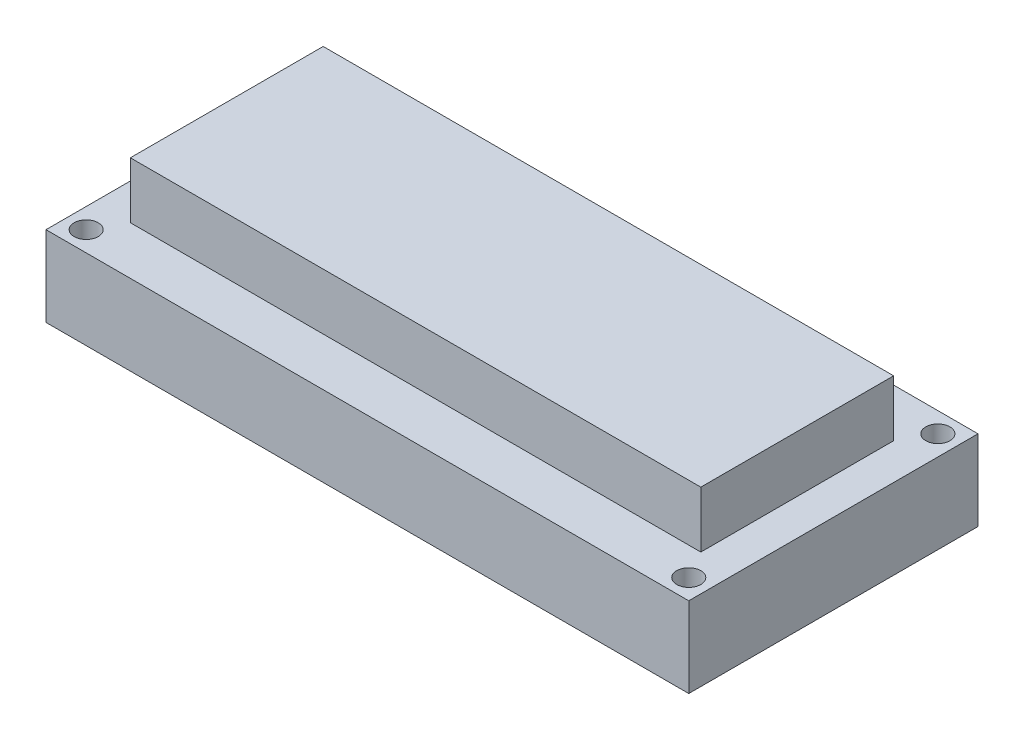
SolidWorks part; units mm, degrees
ref_plane "Front Plane" through (0, 0, 0) normal (0, 0, 1) x (1, 0, 0)
ref_plane "Top Plane" through (0, 0, 0) normal (0, 1, 0) x (1, 0, 0)
ref_plane "Right Plane" through (0, 0, 0) normal (1, 0, 0) x (0, 0, -1)
sketch "Sketch1" plane through (0, 0, 0) normal (0, 1, 0) x (1, 0, 0)
  line L1 (40, -18) -> (-40, -18)
  line L2 (40, -18) -> (40, 18)
  line L3 (40, 18) -> (-40, 18)
  line L4 (-40, -18) -> (-40, 18)
  line L5 (40, -18) -> (-40, 18) construction
  line L6 (40, 18) -> (-40, -18) construction
  line L7 (35.5, -12) -> (-35.5, -12)
  line L8 (35.5, -12) -> (35.5, 12)
  line L9 (35.5, 12) -> (-35.5, 12)
  line L10 (-35.5, -12) -> (-35.5, 12)
  line L11 (35.5, -12) -> (-35.5, 12) construction
  line L12 (35.5, 12) -> (-35.5, -12) construction
  line L13 (-37.5, -15.5) -> (37.5, -15.5) construction
  line L14 (-37.5, -15.5) -> (-37.5, 15.5) construction
  line L15 (-37.5, 15.5) -> (37.5, 15.5) construction
  line L16 (37.5, -15.5) -> (37.5, 15.5) construction
  line L17 (-37.5, -15.5) -> (37.5, 15.5) construction
  line L18 (-37.5, 15.5) -> (37.5, -15.5) construction
  circle A0 centre (37.5, 15.5) radius 1.5
  circle A1 centre (37.5, -15.5) radius 1.5
  circle A2 centre (-37.5, -15.5) radius 1.5
  circle A3 centre (-37.5, 15.5) radius 1.5
  point P0 (0, 0)
  point P6 (0, 0)
  point P11 (0, 0)
  dimension "D7" = 3
  dimension "D1" = 36
  dimension "D2" = 80
  dimension "D3" = 71
  dimension "D4" = 24
  dimension "D5" = 31
  dimension "D6" = 75
extrude "Boss-Extrude1" add sketch "Sketch1" against normal blind 10 contours L10 L7 L8 L9 | L4 L1 L2 L3 A3 A2 A1 A0 L7 L10 L9 L8 region at (0, 0, 17.1227) region at (0, 0, 0)
extrude "Boss-Extrude2" add sketch "Sketch1<3>" along normal blind 7 contours L10 L7 L8 L9 region at (0, 0, 0)
sketch "Sketch1<3>" plane through (0, 0, 0) normal (0, 1, 0) x (1, 0, 0) same geometry as "Sketch1"
sketch "Sketch2" plane through (0, 0, 0) normal (0, 1, 0) x (1, 0, 0)
  line L0 (-35.5, -12) -> (-35.5, 12) construction
  line L1 (-35.5, -12) -> (-35.5, 12)
  line L2 (-35.5, 0) -> (-38.5, 0) construction
  line L3 (-38.5, -1.5) -> (-38.5, 1.5)
  line L4 (-38.5, 1.5) -> (-35.5, 4)
  line L5 (-38.5, -1.5) -> (-35.5, -4)
  line M4 (-35.5, -12) -> (-35.5, 12)
  dimension "D1" = 3
  dimension "D2" = 8
  dimension "D3" = 3
extrude "Boss-Extrude3" add sketch "Sketch2" along normal blind 3 contours L1 L2 L3 L5 | L2 L4 L3 M4 region at (-36.7727, 0, 1.4697) region at (-36.7727, 0, -1.4697)
